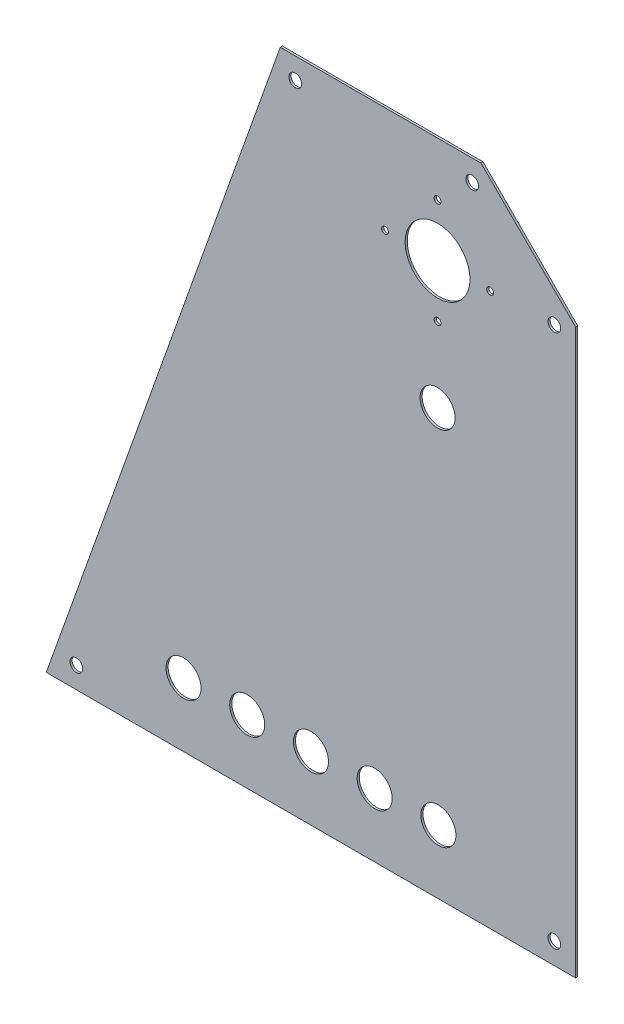
SolidWorks part; units mm, degrees
ref_plane "Front Plane" through (0, 0, 0) normal (1, 0, 0) x (0, 1, 0)
ref_plane "Top Plane" through (0, 0, 0) normal (0, 0, 1) x (0, 1, 0)
ref_plane "Right Plane" through (0, 0, 0) normal (0, 1, 0) x (-1, 0, 0)
sketch "Sketch1" plane through (0, 0, 0) normal (0, 0, 1) x (0, 1, 0)
  line L1 (-155, -125) -> (155, -125)
  line L2 (-155, -125) -> (-155, 125)
  line L3 (-155, 125) -> (155, 125)
  line L4 (155, -125) -> (155, 125)
  line L5 (-155, -125) -> (155, 125) construction
  line L6 (-155, 125) -> (155, -125) construction
  point P0 (0, 0)
  dimension "D1" = 310
  dimension "D2" = 250
extrude "Boss-Extrude1" add sketch "Sketch1" along normal blind 1
sketch "Sketch2" plane through (0, 0, 1) normal (0, 0, 1) x (0, -1, 0)
  line L0 (-155, -14.0477) -> (155, -124.2339)
  line L1 (-155, 125) -> (-155, -125) construction
  line L4 (155, -124.2339) -> (155, 125)
  line L5 (155, 125) -> (-110.4523, 125)
  line L6 (155, 125) -> (-155, 125) construction
  line L7 (-110.4523, 125) -> (-155, 80.4523)
  line L8 (-155, 80.4523) -> (-155, -14.0477)
  line L9 (-155, 80.4523) -> (-155, 125) construction
  line L10 (-155, 125) -> (-110.4523, 125) construction
  dimension "D1" = 63
  dimension "D2" = 329
  dimension "D3" = 94.5
extrude "Cut-Extrude1" cut sketch "Sketch2" against normal through all flip side to cut
sketch "Sketch3" plane through (0, 0, 1) normal (0, 0, 1) x (0, -1, 0)
  line L0 (-155, 60) -> (155, 60) construction
  line L2 (155, -124.2339) -> (155, 125) construction
  line L3 (155, 125) -> (-110.4523, 125) construction
  line L4 (-155, 80.4523) -> (-155, -14.0477) construction
  line L5 (-155, 60) -> (-105, 60) construction
  line L6 (-105, 60) -> (-105, 125) construction
  line L7 (-105, 35.2513) -> (-80.2513, 60) construction
  line L8 (-80.2513, 60) -> (-105, 84.7487) construction
  line L9 (-105, 84.7487) -> (-129.7487, 60) construction
  line L10 (-129.7487, 60) -> (-105, 35.2513) construction
  circle A0 centre (-105, 60) radius 15.25
  circle A1 centre (-45, 60) radius 8.25
  circle A3 centre (-105, 35.2513) radius 1.6
  circle A4 centre (-129.7487, 60) radius 1.6
  circle A5 centre (-105, 84.7487) radius 1.6
  circle A6 centre (-80.2513, 60) radius 1.6
  point P4 (0, 0)
  point P5 (0, 0)
  point P18 (0, 0)
  dimension "D2" = 30.5
  dimension "D1" = 16.5
  dimension "D8" = 3.2
  dimension "D4" = 60
  dimension "D6" = 90
  dimension "D7" = 35
  dimension "D9" = 65
  dimension "D10" = 50
extrude "Cut-Extrude2" cut sketch "Sketch3" against normal through all
sketch "Sketch4" plane through (0, 0, 1) normal (0, 0, 1) x (0, -1, 0)
  line L0 (125, -113.5708) -> (125, 125) construction
  line L1 (-155, -14.0477) -> (155, -124.2339) construction
  line L2 (155, 125) -> (-110.4523, 125) construction
  line L3 (155, -124.2339) -> (155, 125) construction
  circle A0 centre (125, -59.617) radius 8.25
  circle A1 centre (125, -29.617) radius 8.25
  circle A2 centre (125, 0.383) radius 8.25
  circle A3 centre (125, 30.383) radius 8.25
  circle A4 centre (125, 60.383) radius 8.25
  point P22 (155, 0.383)
  dimension "D2" = 16.5
  dimension "D3" = 30
  dimension "D4" = 30
  dimension "D5" = 30
  dimension "D6" = 30
  dimension "D1" = 30
extrude "Cut-Extrude3" cut sketch "Sketch4" against normal through all
sketch "Sketch5" plane through (0, 0, 1) normal (0, 0, 1) x (0, -1, 0)
  line L0 (155, -124.2339) -> (155, 125) construction
  line L3 (155, 125) -> (-110.4523, 125) construction
  line L4 (-155, 80.4523) -> (-155, -14.0477) construction
  line L5 (-155, -14.0477) -> (155, -124.2339) construction
  line L6 (-110.4523, 125) -> (-155, 80.4523) construction
  circle A0 centre (145, -110.0666) radius 3
  circle A1 centre (-145, -6.9892) radius 3
  circle A2 centre (-145, 76.3101) radius 3
  circle A3 centre (145, 115) radius 3
  circle A4 centre (-106.3101, 115) radius 3
  dimension "D1" = 6
  dimension "D2" = 10
  dimension "D3" = 10
  dimension "D4" = 10
  dimension "D5" = 10
  dimension "D6" = 10
  dimension "D7" = 10
  dimension "D8" = 10
  dimension "D9" = 10
  dimension "D10" = 10
  dimension "D11" = 10
extrude "Cut-Extrude4" cut sketch "Sketch5" against normal through all
